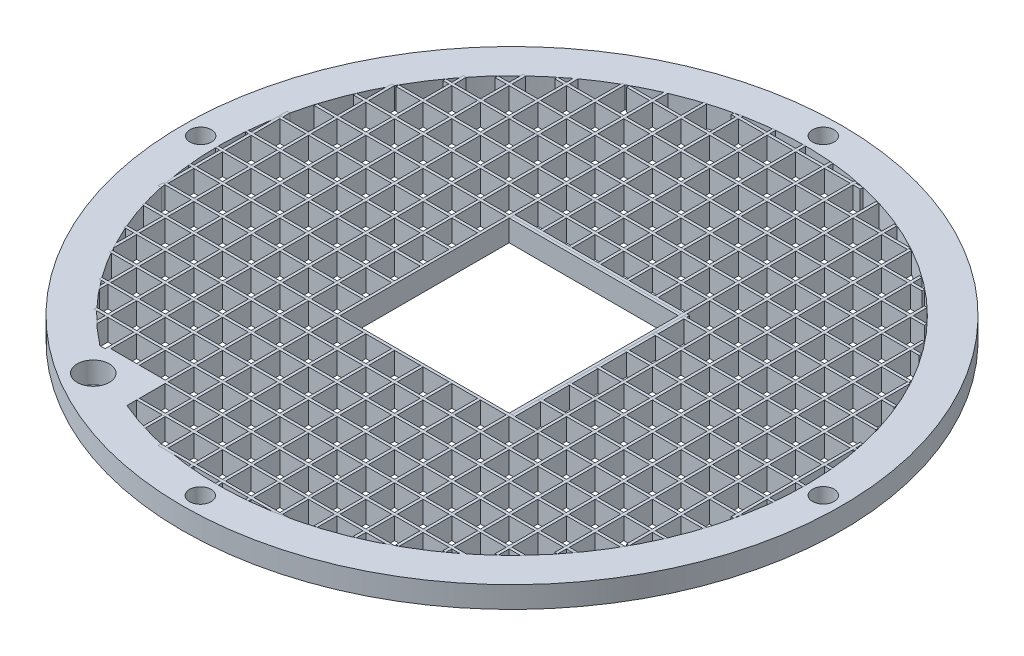
SolidWorks part; units mm, degrees
ref_plane "Front Plane" through (0, 0, 0) normal (0, 0, 1) x (1, 0, 0)
ref_plane "Top Plane" through (0, 0, 0) normal (0, 1, 0) x (1, 0, 0)
ref_plane "Right Plane" through (0, 0, 0) normal (1, 0, 0) x (0, 0, -1)
sketch "Sketch2" plane through (0, 0, 0) normal (0, 1, 0) x (1, 0, 0)
  circle A1 centre (0, 0) radius 41
  circle A2 centre (0, 0) radius 46
  point P208 (0, 0)
extrude "Boss-Extrude2" add sketch "Sketch2" along normal blind 3
sketch "Sketch4" plane through (0, 3, 0) normal (0, 1, 0) x (1, 0, 0)
  line L0 (0, 41) -> (0, 12)
  line L1 (4, 40.8044) -> (4, 12)
  line L2 (8, 40.2119) -> (8, 12)
  line L3 (12, 39.2046) -> (12, -39.2046)
  line L4 (16, 37.7492) -> (16, -37.7492)
  line L5 (20, 35.7911) -> (20, -35.7911)
  line L6 (24, 33.2415) -> (24, -33.2415)
  line L7 (28, 29.95) -> (28, -29.95)
  line L8 (32, 25.632) -> (32, -25.632)
  line L9 (36, 19.6214) -> (36, -19.6214)
  line L10 (40, 9) -> (40, -9)
  line L11 (-41, 0) -> (-12, 0)
  line L12 (-4, 40.8044) -> (-4, 12)
  line L13 (-8, 40.2119) -> (-8, 12)
  line L14 (-12, 39.2046) -> (-12, -39.2046)
  line L15 (-16, 37.7492) -> (-16, -37.7492)
  line L16 (-20, 35.7911) -> (-20, -32)
  line L17 (-24, 33.2415) -> (-24, -32)
  line L18 (-28, 29.95) -> (-28, -29.95)
  line L19 (-32, 25.632) -> (-32, -25.632)
  line L20 (-36, 19.6214) -> (-36, -19.6214)
  line L21 (-40, 9) -> (-40, -9)
  line L22 (-40.8042, -4) -> (-12, -4)
  line L23 (-8, -12) -> (-8, -40.2119)
  line L24 (12, -8) -> (40.2119, -8)
  line L25 (-40.2119, -8) -> (-12, -8)
  line L26 (-39.2046, -12) -> (39.2046, -12)
  line L27 (-37.7492, -16) -> (37.7492, -16)
  line L28 (-35.7911, -20) -> (35.7911, -20)
  line L29 (-33.2415, -24) -> (33.2415, -24)
  line L30 (-29.95, -28) -> (29.95, -28)
  line L31 (-24, -32) -> (25.632, -32)
  line L32 (-16, -36) -> (19.6214, -36)
  line L33 (-9, -40) -> (9, -40)
  line L34 (-9, 40) -> (9, 40)
  line L35 (-19.6214, 36) -> (19.6214, 36)
  line L36 (-25.632, 32) -> (25.632, 32)
  line L37 (-29.95, 28) -> (29.95, 28)
  line L38 (-33.2415, 24) -> (33.2415, 24)
  line L39 (-35.7911, 20) -> (35.7911, 20)
  line L40 (-37.7492, 16) -> (37.7492, 16)
  line L41 (-39.2046, 12) -> (39.2046, 12)
  line L42 (-40.2119, 8) -> (-12, 8)
  line L43 (-40.8042, 4) -> (-12, 4)
  line L44 (12, -4) -> (40.8042, -4)
  line L45 (-12, 12) -> (12, 12)
  line L46 (-12, 12) -> (-12, -12)
  line L47 (-12, -12) -> (12, -12)
  line L48 (12, 12) -> (12, -12)
  line L51 (12, 0) -> (41, 0)
  line L53 (12, 8) -> (40.2119, 8)
  line L54 (-4, -12) -> (-4, -40.8044)
  line L55 (4, -12) -> (4, -40.8044)
  line L56 (0, -12) -> (0, -41)
  line L57 (8, -12) -> (8, -40.2119)
  line L58 (12, 4) -> (40.8042, 4)
  circle A0 centre (0, 0) radius 41 construction
  point P6 (0, 0)
extrude "Extrude-Thin5" add sketch "Sketch4" against normal blind 3 separate body thin thin type one direction wall 0.4
sketch "Sketch5" plane through (0, 0, 0) normal (0, -1, 0) x (1, 0, 0)
  circle A0 centre (0, -43.4524) radius 1.5
  circle A1 centre (-43.4524, 0) radius 1.5
  circle A3 centre (43.4524, 0) radius 1.5
  circle A4 centre (0, 43.4524) radius 1.5 [skipped]
  point P11 (0, 0)
  dimension "D1" = 4
extrude "Cut-Extrude1" cut sketch "Sketch5" against normal blind 3
sketch "Sketch6" plane through (0, 3, 0) normal (0, 1, 0) x (1, 0, 0)
  circle A1 centre (0, -43.5) radius 1.5
  point P36 (0, 3)
  dimension "D1" = 43.5
extrude "Cut-Extrude2" cut sketch "Sketch6" against normal through all
sketch "Sketch8" plane through (0, 3, 0) normal (0, 1, 0) x (1, 0, 0)
  line L0 (-16.4, 37.7492) -> (-16.4, -37.7492) construction
  line L1 (-16.4, -32.4) -> (-25.4613, -32.4)
  line L2 (-16.4, -32.4) -> (-16.4, -37.5484)
  line L3 (-16.4, -37.5484) -> (-25.4613, -37.5484)
  line L4 (-25.4613, -32.4) -> (-25.4613, -37.5484)
  line L5 (-24.4, -32.4) -> (25.632, -32.4) construction
extrude "Boss-Extrude4" add sketch "Sketch8" against normal through all
sketch "Sketch9" plane through (0, 3, 0) normal (0, 1, 0) x (1, 0, 0)
  circle A2 centre (-22.2697, -36.1812) radius 2.25 construction
  circle A3 centre (-22.2697, -36.1812) radius 2.25
extrude "Cut-Extrude3" cut sketch "Sketch9" against normal through all
